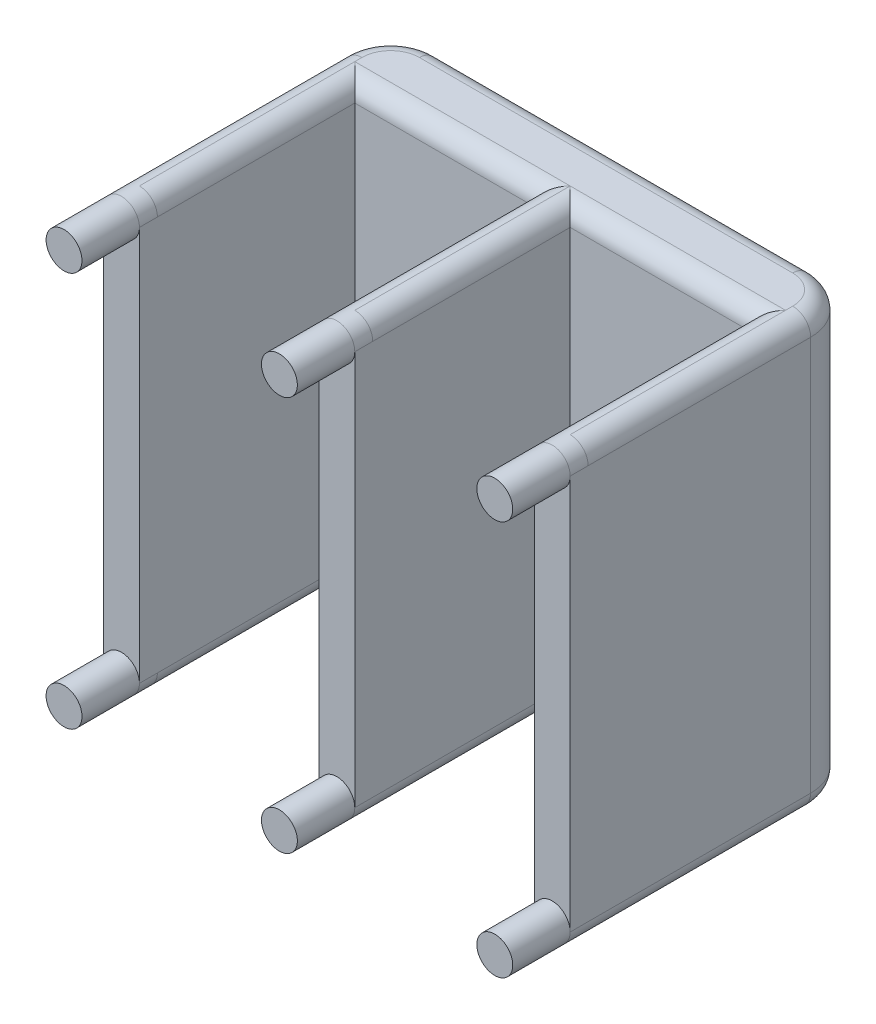
SolidWorks part; units mm, degrees
material "ABS"
ref_plane "Front Plane" through (0, 0, 0) normal (0, 0, 1) x (1, 0, 0)
ref_plane "Top Plane" through (0, 0, 0) normal (0, 1, 0) x (1, 0, 0)
ref_plane "Right Plane" through (0, 0, 0) normal (1, 0, 0) x (0, 0, -1)
sketch "Sketch1" plane through (0, 0, 0) normal (0, 1, 0) x (1, 0, 0)
  line L0 (44.45, 38.1) -> (76.2, 38.1)
  line L1 (0, 0) -> (6.35, 0)
  line L2 (0, 0) -> (0, 38.1)
  line L4 (6.35, 0) -> (6.35, 38.1)
  line L5 (38.1, 0) -> (44.45, 0)
  line L6 (38.1, 0) -> (38.1, 38.1)
  line L8 (44.45, 0) -> (44.45, 38.1)
  line L9 (76.2, 0) -> (82.55, 0)
  line L10 (76.2, 0) -> (76.2, 38.1)
  line L12 (82.55, 0) -> (82.55, 38.1)
  line L17 (6.35, 38.1) -> (38.1, 38.1)
  line L18 (0, 38.1) -> (0, 50.8)
  line L19 (0, 50.8) -> (82.55, 50.8)
  line L22 (82.55, 38.1) -> (82.55, 50.8)
  dimension "D2" = 31.75
  dimension "D3" = 31.75
  dimension "D4" = 38.1
  dimension "D5" = 38.1
  dimension "D6" = 38.1
  dimension "D7" = 6.35
  dimension "D8" = 6.35
  dimension "D9" = 6.35
  dimension "D11" = 12.7
extrude "Boss-Extrude1" add sketch "Sketch1" along normal blind 76.2
sketch "Sketch3" plane through (0, 0, 0) normal (0, 0, 1) x (1, 0, 0)
  line L0 (38.1, 76.2) -> (44.45, 76.2) construction
  line L1 (0, 76.2) -> (6.35, 76.2) construction
  line L2 (76.2, 76.2) -> (82.55, 76.2) construction
  line L3 (0, 0) -> (6.35, 0) construction
  line L4 (38.1, 0) -> (44.45, 0) construction
  line L5 (76.2, 0) -> (82.55, 0) construction
  circle A0 centre (3.175, 73.025) radius 3.175
  circle A1 centre (3.175, 3.175) radius 3.175
  circle A2 centre (41.275, 3.175) radius 3.175
  circle A3 centre (79.375, 3.175) radius 3.175
  circle A4 centre (41.275, 73.025) radius 3.175
  circle A5 centre (79.375, 73.025) radius 3.175
  dimension "D1" = 3.175
  dimension "D2" = 3.175
  dimension "D3" = 3.175
  dimension "D4" = 3.175
  dimension "D5" = 3.175
  dimension "D6" = 3.175
extrude "Boss-Extrude3" add sketch "Sketch3" along normal blind 10.16
fillet "Fillet2" radius 3.175 18 edges at (6.35, 0, -19.05) (22.225, 0, -38.1) (38.1, 0, -19.05) (44.45, 0, -19.05) (60.325, 0, -38.1) (76.2, 0, -19.05) (82.55, 0, -25.4) (41.275, 0, -50.8) (0, 0, -25.4) (41.275, 76.2, -50.8) (82.55, 76.2, -25.4) (76.2, 76.2, -19.05) (60.325, 76.2, -38.1) (44.45, 76.2, -19.05) (38.1, 76.2, -19.05) (22.225, 76.2, -38.1) (6.35, 76.2, -19.05) (0, 76.2, -25.4)
fillet "Fillet3" radius 8.255 6 edges at (0.9299, 0.9299, -49.8701) (0.9299, 75.2701, -49.8701) (81.6201, 0.9299, -49.8701) (81.6201, 75.2701, -49.8701) (82.55, 38.1, -50.8) (0, 38.1, -50.8)
